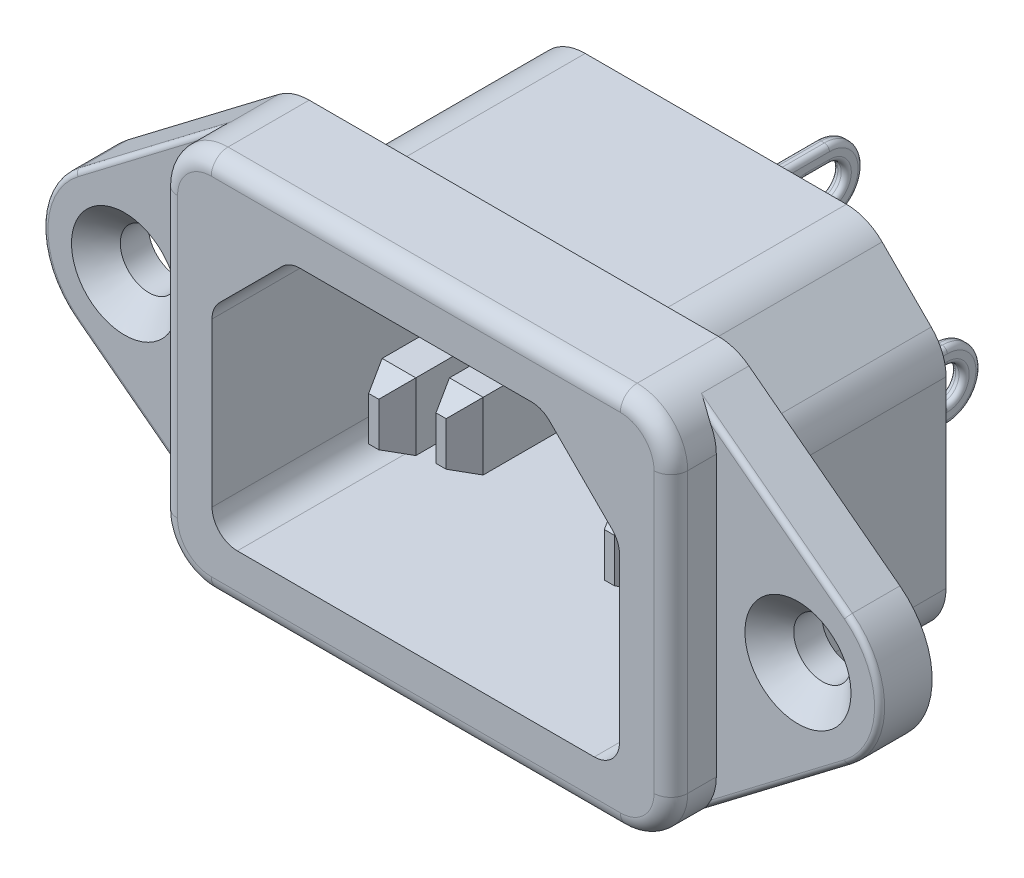
SolidWorks part; units mm, degrees
note: The reader was unsure of these and kept them because the rebuilt part matched: shared geometry of "Эскиз1<3>", "Эскиз12<3>".
ref_plane "Спереди" through (0, 0, 0) normal (0, 0, 1) x (1, 0, 0)
ref_plane "Сверху" through (0, 0, 0) normal (0, 1, 0) x (1, 0, 0)
ref_plane "Справа" through (0, 0, 0) normal (1, 0, 0) x (0, 0, -1)
sketch "Эскиз1" plane through (0, 0, 0) normal (0, 0, 1) x (1, 0, 0)
  line L0 (13.967, 10.6872) -> (22.9375, 3.8592)
  line L1 (-12.15, -11.3) -> (12.15, -11.3)
  line L3 (-12.15, 11.3) -> (12.15, 11.3)
  line L5 (-15.15, -11.3) -> (15.15, 11.3) construction
  line L6 (-15.15, 11.3) -> (15.15, -11.3) construction
  line L7 (22.9375, -3.8592) -> (13.967, -10.6872)
  line L8 (-13.967, 10.6872) -> (-22.9375, 3.8592)
  line L9 (-22.9375, -3.8592) -> (-13.967, -10.6872)
  line L10 (-15.15, 8.3) -> (-15.15, -8.3)
  line L11 (15.15, 8.3) -> (15.15, -8.3)
  line L12 (-20, 0) -> (20, 0) construction
  arc A0 (22.9375, 3.8592) -> (22.9375, -3.8592) centre (20, 0) cw
  arc A1 (-22.9375, 3.8592) -> (-22.9375, -3.8592) centre (-20, 0) ccw
  arc A2 (-12.15, -11.3) -> (-15.15, -8.3) centre (-12.15, -8.3) cw
  arc A3 (12.15, -11.3) -> (15.15, -8.3) centre (12.15, -8.3) ccw
  arc A4 (12.15, 11.3) -> (15.15, 8.3) centre (12.15, 8.3) cw
  arc A5 (-12.15, 11.3) -> (-15.15, 8.3) centre (-12.15, 8.3) ccw
  point P0 (0, 0)
  dimension "D2" = 49.7
  dimension "D4" = 40
  dimension "D5" = 3
  dimension "D1" = 22.6
  dimension "D3" = 30.3
extrude "Бобышка-Вытянуть1" add sketch "Эскиз1" along normal blind 3.12 contours A5 L8 A1 L9 A2 L10 | L3 A5 L10 A2 L1 A3 L11 A4 | L0 A4 L11 A3 L7 A0
extrude "Бобышка-Вытянуть2" add sketch "Эскиз1<3>" along normal blind 2.7 from surface at 3.12 contours L3 A4 L11 A3 L1 A2 L10 A5 starting at face at (0, 0, 3.12)
sketch "Эскиз1<3>" plane through (0, 0, 0) normal (0, 0, 1) x (1, 0, 0) same geometry as "Эскиз1"
sketch "Эскиз3" plane through (0, 0, 0) normal (0, 0, -1) x (-1, 0, 0)
  line L5 (-13.675, -6.9) -> (-13.675, 3.9824)
  line L6 (-12.7963, 6.1037) -> (-9.8787, 9.0213)
  line L8 (-7.7574, 9.9) -> (7.7574, 9.9)
  line L9 (9.8787, 9.0213) -> (12.7963, 6.1037)
  line L10 (13.675, 3.9824) -> (13.675, -6.9)
  line L11 (10.675, -9.9) -> (-10.675, -9.9)
  line L12 (0, 9.9) -> (0, -9.9) construction
  arc A6 (-13.675, 3.9824) -> (-12.7963, 6.1037) centre (-10.675, 3.9824) cw
  arc A7 (-9.8787, 9.0213) -> (-7.7574, 9.9) centre (-7.7574, 6.9) cw
  arc A8 (7.7574, 9.9) -> (9.8787, 9.0213) centre (7.7574, 6.9) cw
  arc A9 (12.7963, 6.1037) -> (13.675, 3.9824) centre (10.675, 3.9824) cw
  arc A10 (13.675, -6.9) -> (10.675, -9.9) centre (10.675, -6.9) cw
  arc A11 (-13.675, -6.9) -> (-10.675, -9.9) centre (-10.675, -6.9) ccw
  point P11 (-13.675, 5.225)
  point P14 (-9, 9.9)
  point P17 (9, 9.9)
  point P20 (13.675, 5.225)
  dimension "D5" = 3
  dimension "D1" = 45
  dimension "D2" = 18
  dimension "D3" = 19.8
  dimension "D4" = 27.35
extrude "Бобышка-Вытянуть3" add sketch "Эскиз3" along normal blind 12
sketch "Эскиз4" plane through (0, 0, 5.82) normal (0, 0, 1) x (1, 0, 0)
  line L0 (-11.6607, 4.0393) -> (-7.9393, 7.7607)
  line L1 (-6.8787, 8.2) -> (6.8787, 8.2)
  line L2 (7.9393, 7.7607) -> (11.6607, 4.0393)
  line L3 (12.1, 2.9787) -> (12.1, -6.7)
  line L4 (10.6, -8.2) -> (-10.6, -8.2)
  line L5 (-12.1, -6.7) -> (-12.1, 2.9787)
  line L6 (0, 8.2) -> (0, -8.2) construction
  arc A0 (-11.6607, 4.0393) -> (-12.1, 2.9787) centre (-10.6, 2.9787) ccw
  arc A1 (-7.9393, 7.7607) -> (-6.8787, 8.2) centre (-6.8787, 6.7) cw
  arc A2 (6.8787, 8.2) -> (7.9393, 7.7607) centre (6.8787, 6.7) cw
  arc A3 (11.6607, 4.0393) -> (12.1, 2.9787) centre (10.6, 2.9787) cw
  arc A4 (12.1, -6.7) -> (10.6, -8.2) centre (10.6, -6.7) cw
  arc A5 (-10.6, -8.2) -> (-12.1, -6.7) centre (-10.6, -6.7) cw
  point P13 (-12.1, 3.6)
  point P16 (-7.5, 8.2)
  point P19 (7.5, 8.2)
  point P22 (12.1, 3.6)
  dimension "D5" = 1.5
  dimension "D1" = 45
  dimension "D2" = 24.2
  dimension "D3" = 16.4
  dimension "D4" = 15
extrude "Вырез-Вытянуть1" cut sketch "Эскиз4" against normal blind 16
sketch "Эскиз5" plane through (0, 0, -12) normal (0, 0, -1) x (-1, 0, 0)
  line L0 (7, -3.475) -> (-7, -3.475) construction
  line L1 (-7, -3.475) -> (0, 3.475) construction
  line L2 (0, 3.475) -> (7, -3.475) construction
  line L3 (0, -3.475) -> (0, 3.475) construction
  line L4 (-10.675, -9.9) -> (10.675, -9.9) construction
  line L5 (8.5, -7.65) -> (5.5, -7.65)
  line L6 (9.5, -6.65) -> (9.5, -0.3)
  line L7 (8.5, 0.7) -> (5.5, 0.7)
  line L8 (4.5, -6.65) -> (4.5, -0.3)
  line L9 (9.5, -7.65) -> (4.5, 0.7) construction
  line L10 (9.5, 0.7) -> (4.5, -7.65) construction
  line L11 (-5.5, -7.65) -> (-8.5, -7.65)
  line L12 (-4.5, -6.65) -> (-4.5, -0.3)
  line L13 (-5.5, 0.7) -> (-8.5, 0.7)
  line L14 (-9.5, -6.65) -> (-9.5, -0.3)
  line L15 (-4.5, -7.65) -> (-9.5, 0.7) construction
  line L16 (-4.5, 0.7) -> (-9.5, -7.65) construction
  line L17 (1.5, -0.7) -> (-1.5, -0.7)
  line L18 (2.5, 0.3) -> (2.5, 6.65)
  line L19 (1.5, 7.65) -> (-1.5, 7.65)
  line L20 (-2.5, 0.3) -> (-2.5, 6.65)
  line L21 (2.5, -0.7) -> (-2.5, 7.65) construction
  line L22 (2.5, 7.65) -> (-2.5, -0.7) construction
  line L23 (7.7574, 9.9) -> (-7.7574, 9.9) construction
  arc A0 (-5.5, -7.65) -> (-4.5, -6.65) centre (-5.5, -6.65) ccw
  arc A1 (-8.5, -7.65) -> (-9.5, -6.65) centre (-8.5, -6.65) cw
  arc A2 (-8.5, 0.7) -> (-9.5, -0.3) centre (-8.5, -0.3) ccw
  arc A3 (-4.5, -0.3) -> (-5.5, 0.7) centre (-5.5, -0.3) ccw
  arc A4 (2.5, 6.65) -> (1.5, 7.65) centre (1.5, 6.65) ccw
  arc A5 (-1.5, 7.65) -> (-2.5, 6.65) centre (-1.5, 6.65) ccw
  arc A6 (-1.5, -0.7) -> (-2.5, 0.3) centre (-1.5, 0.3) cw
  arc A7 (1.5, -0.7) -> (2.5, 0.3) centre (1.5, 0.3) ccw
  arc A8 (5.5, 0.7) -> (4.5, -0.3) centre (5.5, -0.3) ccw
  arc A9 (9.5, -0.3) -> (8.5, 0.7) centre (8.5, -0.3) ccw
  arc A10 (8.5, -7.65) -> (9.5, -6.65) centre (8.5, -6.65) ccw
  arc A11 (5.5, -7.65) -> (4.5, -6.65) centre (5.5, -6.65) cw
  dimension "D6" = 1
  dimension "D1" = 5
  dimension "D2" = 8.35
  dimension "D3" = 14
  dimension "D4" = 2.25
  dimension "D5" = 2.25
extrude "Бобышка-Вытянуть4" add sketch "Эскиз5" along normal blind 2.2
hole_wizard "Зенковка для винта с полупотайной головкой M31" positions "Эскиз6" profile "Эскиз7" countersink size "M3" standard "DIN"
sketch "Эскиз6" plane through (0, 0, 3.12) normal (0, 0, 1) x (1, 0, 0)
  line L0 (-20, 0) -> (20, 0) construction
  point P11 (-20, 0)
  point P13 (20, 0)
  dimension "D1" = 40
sketch "Эскиз7" plane through (-20, 0, 3.12) normal (1, 0, 0) x (0, -1, 0)
  line L0 (0, 0) -> (0, 6.0215)
  line L1 (0, 6.0215) -> (1.7, 5)
  line L2 (1.7, 5) -> (1.7, 1.45)
  line L3 (1.7, 1.45) -> (3.15, 0)
  line L5 (3.15, 0) -> (0, 0)
  line L6 (-1.7, 1.45) -> (-3.15, 0) construction
  line L10 (0, 6.0215) -> (-1.7, 5) construction
  line L11 (0, -6.35) -> (0, 107.95) construction
  dimension "Диаметр отверстия" = 3.4
  dimension "Глубина отверстия" = 5
  dimension "Диаметр передней зенковки" = 6.3
  dimension "Угол передней зенковки" = 90
  dimension "Угол заточки сверла" = 118
sketch "Эскиз8" plane through (0, 0, -14.2) normal (0, 0, -1) x (-1, 0, 0)
  line L0 (-7, -3.45) -> (0, 3.45) construction
  line L1 (-1, 5.45) -> (1, 5.45)
  line L2 (-1, 5.45) -> (-1, 1.45)
  line L3 (-1, 1.45) -> (1, 1.45)
  line L4 (1, 5.45) -> (1, 1.45)
  line L5 (-1, 5.45) -> (1, 1.45) construction
  line L6 (-1, 1.45) -> (1, 5.45) construction
  line L7 (6, -1.45) -> (8, -1.45)
  line L8 (6, -1.45) -> (6, -5.45)
  line L9 (6, -5.45) -> (8, -5.45)
  line L10 (8, -1.45) -> (8, -5.45)
  line L11 (6, -1.45) -> (8, -5.45) construction
  line L12 (6, -5.45) -> (8, -1.45) construction
  line L13 (-8, -1.45) -> (-6, -1.45)
  line L14 (-8, -1.45) -> (-8, -5.45)
  line L15 (-8, -5.45) -> (-6, -5.45)
  line L16 (-6, -1.45) -> (-6, -5.45)
  line L17 (-8, -1.45) -> (-6, -5.45) construction
  line L18 (-8, -5.45) -> (-6, -1.45) construction
  line L19 (0, 3.45) -> (7, -3.45) construction
  line L20 (7, -3.45) -> (-7, -3.45) construction
  line L21 (0, 3.45) -> (0, -3.45) construction
  point P0 (0, 3.45)
  point P5 (7, -3.45)
  point P10 (-7, -3.45)
  dimension "D1" = 2
  dimension "D2" = 4
  dimension "D3" = 14
  dimension "D4" = 10.9
extrude "Бобышка-Вытянуть5" add sketch "Эскиз8" along normal blind 6.75
sketch "Эскиз10" plane through (0, 0, -20.95) normal (0, 0, -1) x (-1, 0, 0)
  line L0 (-1, 1.45) -> (1, 1.45) construction
  line L1 (-1, 5.45) -> (0.2, 5.45)
  line L2 (-1, 5.45) -> (-1, 1.45)
  line L3 (-1, 1.45) -> (0.2, 1.45)
  line L4 (0.2, 5.45) -> (0.2, 1.45)
  line L5 (-8, -5.45) -> (-6, -5.45) construction
  line L6 (-8, -1.45) -> (-6.8, -1.45)
  line L7 (-8, -1.45) -> (-8, -5.45)
  line L8 (-8, -5.45) -> (-6.8, -5.45)
  line L9 (-6.8, -1.45) -> (-6.8, -5.45)
  line L10 (6, -5.45) -> (8, -5.45) construction
  line L11 (6, -1.45) -> (7.2, -1.45)
  line L12 (6, -1.45) -> (6, -5.45)
  line L13 (6, -5.45) -> (7.2, -5.45)
  line L14 (7.2, -1.45) -> (7.2, -5.45)
  line L15 (1, 1.45) -> (1, 5.45) construction
  dimension "D1" = 0.8
extrude "Вырез-Вытянуть3" cut sketch "Эскиз10" against normal offset from surface (5.95 mm away) 0.8 up to face at (0, 3.45, -14.2)
sketch "Эскиз9" plane through (-8, 0, 0) normal (-1, 0, 0) x (0, 0, 1)
  line L0 (-20.95, -1.45) -> (-14.2, -1.45) construction
  line L1 (-20.95, -5.45) -> (-14.2, -5.45) construction
  line L2 (-20.95, -5.45) -> (-20.95, -1.45) construction
  line L3 (-20.95, 5.45) -> (-14.2, 5.45) construction
  line L4 (-20.95, 1.45) -> (-14.2, 1.45) construction
  line L5 (-20.95, 1.45) -> (-20.95, 5.45) construction
  line L6 (-20.95, -5.45) -> (-18.95, -5.45)
  line L7 (-20.95, -5.45) -> (-20.95, -1.45)
  line L8 (-20.95, -1.45) -> (-18.95, -1.45)
  line L9 (-20.95, 1.45) -> (-18.95, 1.45)
  line L10 (-20.95, 1.45) -> (-20.95, 5.45)
  line L11 (-20.95, 5.45) -> (-18.95, 5.45)
  arc A0 (-18.95, -1.45) -> (-18.95, -5.45) centre (-18.95, -3.45) ccw
  arc A1 (-18.95, 5.45) -> (-18.95, 1.45) centre (-18.95, 3.45) ccw
  line M2 (-14.2, -1.45) -> (-20.95, -1.45)
  line M3 (-20.95, -1.45) -> (-20.95, -5.45)
  line M4 (-20.95, -5.45) -> (-14.2, -5.45)
extrude "Вырез-Вытянуть2" cut sketch "Эскиз9" against normal through all contours A1 L10 L9 | A1 L11 L10 | A0 M2 M3 | A0 L7 M4
sketch "Эскиз11" plane through (-8, 0, 0) normal (-1, 0, 0) x (0, 0, 1)
  line L0 (-18.95, -3.45) -> (-17.55, -3.45) construction
  line L1 (-18.95, -2.45) -> (-17.55, -2.45)
  line L2 (-18.95, -4.45) -> (-17.55, -4.45)
  line L3 (-18.95, 3.45) -> (-17.55, 3.45) construction
  line L4 (-18.95, 4.45) -> (-17.55, 4.45)
  line L5 (-18.95, 2.45) -> (-17.55, 2.45)
  arc A0 (-18.95, -2.45) -> (-18.95, -4.45) centre (-18.95, -3.45) ccw
  arc A1 (-17.55, -4.45) -> (-17.55, -2.45) centre (-17.55, -3.45) ccw
  arc A2 (-18.95, 4.45) -> (-18.95, 2.45) centre (-18.95, 3.45) ccw
  arc A3 (-17.55, 2.45) -> (-17.55, 4.45) centre (-17.55, 3.45) ccw
  point P3 (-18.25, -3.45)
  point P8 (-18.25, 3.45)
  dimension "D2" = 3.4
  dimension "D1" = 2
extrude "Вырез-Вытянуть4" cut sketch "Эскиз11" against normal through all
sketch "Эскиз12" plane through (0, 0, -10.18) normal (0, 0, 1) x (1, 0, 0)
  line L0 (-7, -2) -> (7, -2) construction
  line L1 (-1, 0) -> (1, 0)
  line L2 (-1, 0) -> (-1, 4)
  line L3 (-1, 4) -> (1, 4)
  line L4 (1, 0) -> (1, 4)
  line L5 (-1, 0) -> (1, 4) construction
  line L6 (-1, 4) -> (1, 0) construction
  line L7 (6, -4) -> (8, -4)
  line L8 (6, -4) -> (6, 0)
  line L9 (6, 0) -> (8, 0)
  line L10 (8, -4) -> (8, 0)
  line L11 (6, -4) -> (8, 0) construction
  line L12 (6, 0) -> (8, -4) construction
  line L13 (-8, -4) -> (-6, -4)
  line L14 (-8, -4) -> (-8, 0)
  line L15 (-8, 0) -> (-6, 0)
  line L16 (-6, -4) -> (-6, 0)
  line L17 (-8, -4) -> (-6, 0) construction
  line L18 (-8, 0) -> (-6, -4) construction
  line L19 (7, -2) -> (0, 2) construction
  line L20 (0, 2) -> (-7, -2) construction
  line L21 (0, 2) -> (0, -2) construction
  point P0 (0, 2)
  point P5 (7, -2)
  point P10 (-7, -2)
  point P17 (-6.137, -0.7949)
  dimension "D1" = 2
  dimension "D2" = 4
  dimension "D3" = 14
  dimension "D4" = 4
extrude "Бобышка-Вытянуть6" add sketch "Эскиз12" along normal blind 11.5 contours L14 L15 L16 L13 | L8 L9 L10 L7
extrude "Бобышка-Вытянуть7" add sketch "Эскиз12<3>" along normal blind 14.5 contours L2 L3 L4 L1
sketch "Эскиз12<3>" plane through (0, 0, -10.18) normal (0, 0, 1) x (1, 0, 0) same geometry as "Эскиз12"
chamfer "Фаска1" distance 0.7 angle 65 6 edges at (-8, -2, 1.32) (-6, -2, 1.32) (8, -2, 1.32) (6, -2, 1.32) (-1, 2, 4.32) (1, 2, 4.32)
chamfer "Фаска2" distance 0.7 angle 65 6 edges at (-7, 0, 1.32) (-7, -4, 1.32) (7, 0, 1.32) (7, -4, 1.32) (0, 4, 4.32) (0, 0, 4.32)
fillet "Скругление1" radius 1 8 edges at (0, 11.3, 5.82) (14.2713, 10.4213, 5.82) (15.15, 0, 5.82) (14.2713, -10.4213, 5.82) (0, -11.3, 5.82) (-14.2713, -10.4213, 5.82) (-15.15, 0, 5.82) (-14.2713, 10.4213, 5.82)
fillet "Скругление2" radius 0.3 6 edges at (18.4522, -7.2732, 3.12) (24.85, 0, 3.12) (18.4522, 7.2732, 3.12) (-18.4522, 7.2732, 3.12) (-24.85, 0, 3.12) (-18.4522, -7.2732, 3.12)
fillet "Скругление3" radius 0.3 48 edges at (6.8, -1.45, -16.975) (6.8, -5.45, -16.975) (6.8, -4.45, -18.25) (6.8, -3.45, -19.95) (6.8, -2.45, -18.25) (-7.2, -1.45, -16.975) (-7.2, -5.45, -16.975) (-7.2, -4.45, -18.25) (-7.2, -3.45, -19.95) (-7.2, -2.45, -18.25) (6, -5.45, -16.575) (6, -1.45, -16.575) (6, -2.45, -18.25) (6, -3.45, -19.95) (6, -4.45, -18.25) (-8, -4.45, -18.25) (-8, -3.45, -19.95) (-8, -2.45, -18.25) (-8, -1.45, -16.575) (-8, -5.45, -16.575) (-1, 1.45, -16.575) (-1, 5.45, -16.575) (-0.2, 5.45, -16.975) (-0.2, 1.45, -16.975) (-1, 4.45, -18.25) (-1, 3.45, -19.95) (-1, 2.45, -18.25) (-0.2, 2.45, -18.25) (-0.2, 3.45, -19.95) (-0.2, 4.45, -18.25) (-6, -5.45, -14.6) (-6, -1.45, -14.6) (1, 1.45, -14.6) (1, 5.45, -14.6) (8, -5.45, -14.6) (8, -1.45, -14.6) (6.8, -3.45, -20.95) (6.8, -3.45, -16.55) (-7.2, -3.45, -20.95) (-7.2, -3.45, -16.55) (6, -3.45, -20.95) (6, -3.45, -16.55) (-8, -3.45, -16.55) (-8, -3.45, -20.95) (-1, 3.45, -20.95) (-0.2, 3.45, -20.95) (-1, 3.45, -16.55) (-0.2, 3.45, -16.55)
